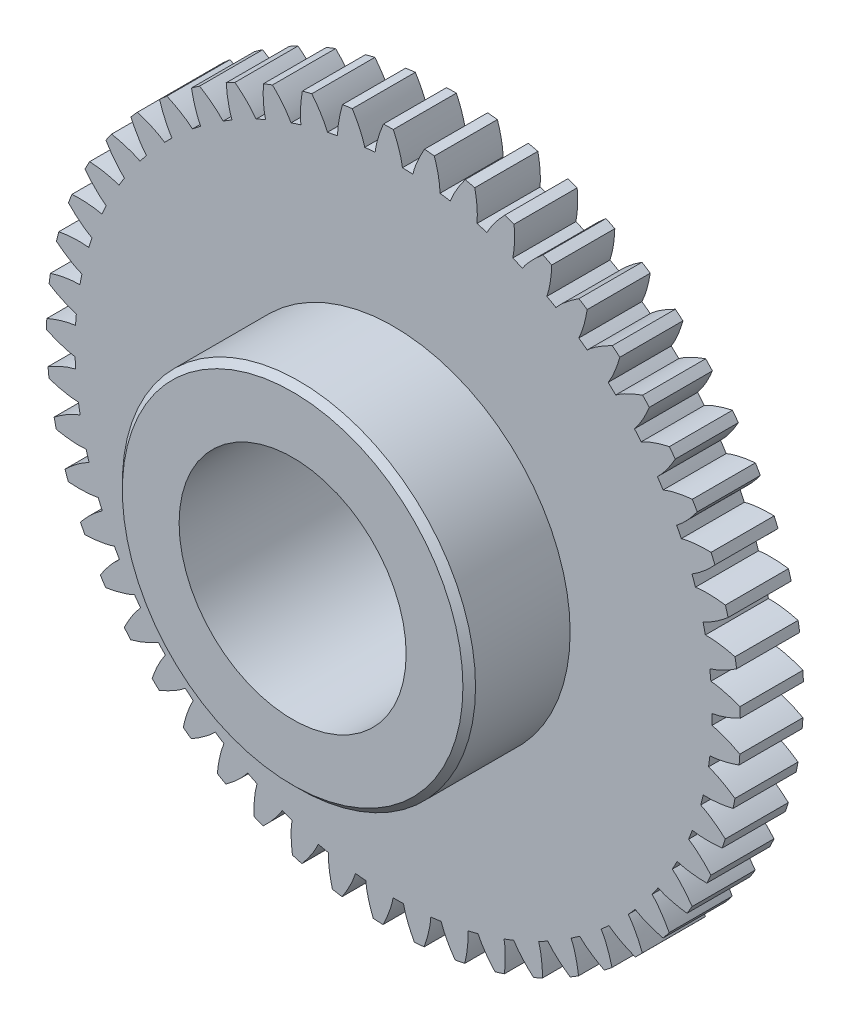
SolidWorks part; units mm, degrees
ref_plane "前视基准面" through (0, 0, 0) normal (0, 0, 1) x (1, 0, 0)
ref_plane "上视基准面" through (0, 0, 0) normal (0, 1, 0) x (1, 0, 0)
ref_plane "右视基准面" through (0, 0, 0) normal (1, 0, 0) x (0, 0, -1)
sketch "草图1" plane through (0, 0, 0) normal (0, 0, 1) x (1, 0, 0)
  circle A0 centre (0, 0) radius 25.25
extrude "凸台-拉伸1" add sketch "草图1" along normal blind 5
sketch "草图2" plane through (0, 0, 0) normal (0, 0, 1) x (1, 0, 0)
  arc A0 (27.4526, 1.6134) -> (27.4873, 0.8353) centre (0, 0) cw
  arc A1 (24.8031, 2.2154) -> (24.9019, 0) centre (0, 0) cw
  spline S0 degree 3 poles (27.4873, 0.8353) (27.2074, 0.6937) (26.7823, 0.4994) (26.2031, 0.2844) (25.6321, 0.1085) (25.1958, 0.0175) (24.9019, 0) knots 0 0 0 0 0.344416 0.512486 0.677795 1 1 1 1
  spline S1 degree 3 poles (27.4526, 1.6134) (27.1612, 1.7296) (26.7205, 1.8853) (26.1245, 2.0479) (25.5401, 2.1724) (25.0975, 2.2242) (24.8031, 2.2154) knots 0 0 0 0 0.344416 0.512486 0.677795 1 1 1 1
extrude "凸台-拉伸2" add sketch "草图2" along normal blind 5
pattern_circular "阵列(圆周)1" count 53 over 360 about axis through (0, 0, 5) along (0, 0, -1) of "凸台-拉伸2"
sketch "草图3" plane through (0, 0, 5) normal (0, 0, 1) x (1, 0, 0)
  circle A0 centre (0, 0) radius 14
  dimension "D1" = 28
extrude "凸台-拉伸3" add sketch "草图3" along normal blind 8
sketch "草图4" plane through (0, 0, 13) normal (0, 0, 1) x (1, 0, 0)
  circle A0 centre (0, 0) radius 9
  dimension "D1" = 18
extrude "切除-拉伸1" cut sketch "草图4" against normal through all
chamfer "倒角1" distance 0.5 angle 45 1 edges at (14, 0, 13)
sketch "草图5" plane through (0, 0, 0) normal (0, 0, -1) x (-1, 0, 0)
  line L0 (0, 0) -> (0, 9) construction
  circle A0 centre (0, 0) radius 9 construction
hole_wizard "M4 螺纹孔2" positions "3D草图2" profile "草图7" tap size "M4" standard "GB"
sketch3d "3D草图2"
  point P0 (0, 9, 0)
sketch "草图7" plane through (0, 9, 0) normal (1, 0, 0) x (0, 1, 0)
  line L0 (0, 0) -> (0, 8)
  line L1 (0, 8) -> (1.65, 7.0086)
  line L2 (1.65, 7.0086) -> (1.65, 0)
  line L5 (1.65, 0) -> (0, 0)
  line L10 (0, 8) -> (-1.65, 7.0086) construction
  line L11 (0, -6.35) -> (0, 107.95) construction
  dimension "螺纹孔钻头直径" = 3.3
  dimension "螺纹孔钻头深度" = 8
  dimension "导头角度" = 118
cosmetic thread "孔螺纹线2" parameters "D1"=7, "D2"=4
